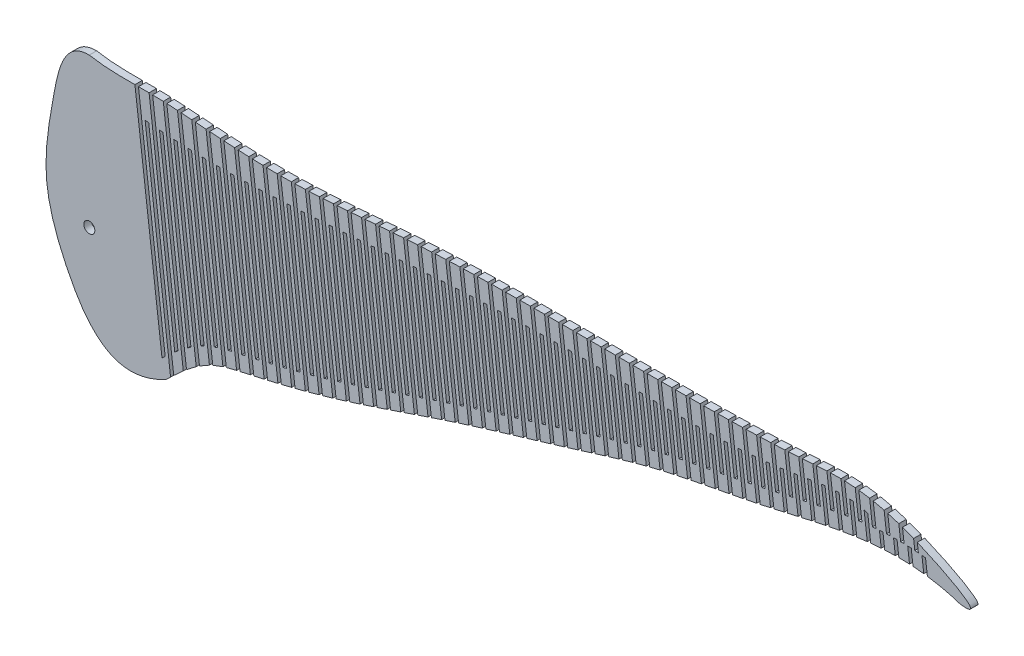
SolidWorks part; units mm, degrees
ref_plane "Front Plane" through (0, 0, 0) normal (0, 0, 1) x (1, 0, 0)
ref_plane "Top Plane" through (0, 0, 0) normal (0, 1, 0) x (1, 0, 0)
ref_plane "Right Plane" through (0, 0, 0) normal (1, 0, 0) x (0, 0, -1)
sketch "Sketch1" plane through (0, 0, 0) normal (0, 0, 1) x (1, 0, 0)
  line L0 (302.5, 350) -> (1512.5, 350) construction
  circle A0 centre (567.1336, 244.6808) radius 2.3812
  spline S0 degree 3 poles (600.4259, 204.6487) (606.7816, 210.8773) (616.6645, 220.058) (640.457, 225.1521) (675.3526, 233.403) (721.2401, 250.3771) (769.3486, 264.0871) (812.9063, 278.2152) (869.1744, 286.9675) (914.4097, 301.2518) (942.415, 291.7005) knots 0.067185 0.067185 0.067185 0.067185 0.134805 0.169915 0.254869 0.416958 0.551289 0.647146 0.774192 1 1 1 1
  spline S1 degree 3 poles (567.1336, 308.9768) (568.72, 308.6788) (577.9261, 307.3771) (593.7513, 308.2492) (620.2471, 306.2074) (657.6694, 303.8802) (709.4341, 310.0538) (762.3439, 310.4228) (816.8394, 310.2811) (875.3509, 310.7032) (908.5345, 316.1056) (953.925, 290.4379) (942.415, 291.7005) knots 0.040646 0.040646 0.040646 0.040646 0.052792 0.110595 0.156897 0.250722 0.388424 0.543858 0.641456 0.800742 0.941142 1 1 1 1
  spline S2 degree 3 poles (571.9268, 308.2818) (556.6626, 312.2623) (551.2163, 284.1495) (546.0116, 252.996) (559.7153, 216.0207) (577.7709, 191.9486) (600.4259, 204.6487) knots 0 0 0 0 0.228542 0.463661 0.652574 1 1 1 1
  dimension "D44" = 4.7625
  dimension "D1" = 548.9986
  dimension "D2" = 551.7183
  dimension "D3" = 557.9576
  dimension "D4" = 559.9938
  dimension "D5" = 567.1336
  dimension "D6" = 571.9268
  dimension "D7" = 595.2442
  dimension "D8" = 600.4259
  dimension "D9" = 613.8982
  dimension "D10" = 621.1525
  dimension "D11" = 634.1066
  dimension "D12" = 651.7242
  dimension "D13" = 665.7147
  dimension "D14" = 707.1679
  dimension "D15" = 724.7856
  dimension "D16" = 769.866
  dimension "D17" = 774.0113
  dimension "D18" = 809.2465
  dimension "D19" = 856.9177
  dimension "D20" = 873.499
  dimension "D21" = 925.8337
  dimension "D22" = 929.4609
  dimension "D23" = 942.415
  dimension "D24" = 946.0422
  dimension "D25" = 204.6487
  dimension "D26" = 220.1937
  dimension "D27" = 223.8208
  dimension "D28" = 231.5933
  dimension "D29" = 250.7654
  dimension "D30" = 265.7922
  dimension "D31" = 276.1555
  dimension "D32" = 286.0007
  dimension "D33" = 291.7005
  dimension "D34" = 295.3277
  dimension "D35" = 303.1001
  dimension "D36" = 305.1728
  dimension "D37" = 306.7273
  dimension "D38" = 307.7636
  dimension "D39" = 308.2818
  dimension "D40" = 308.8
  dimension "D41" = 308.9768
  dimension "D42" = 310.3545
  dimension "D43" = 311.9089
extrude "Boss-Extrude2" add sketch "Sketch1" along normal blind 3.175 contours S1 S2 S0 A0 | S1 S0 S2 region at (685.9886, 273.0456, 0)
sketch "Sketch3" plane through (0, 0, 3.175) normal (0, 0, 1) x (1, 0, 0)
  line L1 (586.2707, 312.0618) -> (598.4557, 211.5854)
  line L2 (587.7923, 312.0816) -> (599.8225, 212.8815)
  line L3 (591.1842, 296.6788) -> (603.0411, 198.9077)
  line L4 (592.7259, 296.5333) -> (604.5144, 199.3261)
  line L5 (592.3571, 312.1409) -> (603.9455, 216.5844)
  line L6 (593.8787, 312.1607) -> (605.3292, 217.741)
  line L7 (597.3447, 296.1474) -> (608.9342, 200.5812)
  line L8 (598.8823, 296.035) -> (610.4075, 200.9996)
  line L9 (598.4435, 312.22) -> (609.5153, 220.923)
  line L10 (599.9651, 312.2398) -> (610.9235, 221.8782)
  line L11 (603.4895, 295.7448) -> (614.8273, 202.2547)
  line L12 (605.0234, 295.6632) -> (616.3005, 202.6731)
  line L13 (604.5299, 312.2991) -> (615.1897, 224.3995)
  line L14 (606.0515, 312.3189) -> (616.6262, 225.1212)
  line L15 (609.6198, 295.4618) -> (620.7203, 203.9282)
  line L16 (611.1503, 295.4087) -> (622.1936, 204.3465)
  line L17 (610.6163, 312.3782) -> (620.9792, 226.9267)
  line L18 (612.1379, 312.398) -> (622.4433, 227.4209)
  line L19 (615.7368, 295.289) -> (626.6134, 205.6017)
  line L20 (617.264, 295.262) -> (628.0866, 206.02)
  line L21 (616.7027, 312.4574) -> (626.8637, 228.6709)
  line L22 (618.2243, 312.4771) -> (628.3439, 229.0317)
  line L23 (621.8415, 295.2173) -> (632.5064, 207.2751)
  line L24 (623.3659, 295.214) -> (633.9797, 207.6935)
  line L25 (622.7891, 312.5365) -> (632.7944, 230.034)
  line L26 (624.3107, 312.5563) -> (634.2786, 230.3625)
  line L27 (627.935, 295.2374) -> (638.3995, 208.9486)
  line L28 (629.4568, 295.2557) -> (639.8727, 209.367)
  line L29 (628.8755, 312.6156) -> (638.7293, 231.3625)
  line L30 (630.3971, 312.6354) -> (640.2122, 231.7014)
  line L31 (634.0185, 295.3404) -> (644.2925, 210.6221)
  line L32 (635.538, 295.3781) -> (645.7658, 211.0405)
  line L33 (634.9619, 312.6947) -> (644.6586, 232.737)
  line L34 (636.4835, 312.7145) -> (646.1399, 233.0892)
  line L35 (640.093, 295.5175) -> (650.1856, 212.2956)
  line L36 (641.6104, 295.5723) -> (651.6588, 212.7139)
  line L37 (641.0483, 312.7738) -> (650.5808, 234.1697)
  line L38 (642.5699, 312.7936) -> (652.0601, 234.5384)
  line L39 (646.1597, 295.7599) -> (656.0786, 213.9691)
  line L40 (647.6752, 295.8296) -> (657.5519, 214.3874)
  line L41 (647.1347, 312.853) -> (656.4945, 235.6732)
  line L42 (648.6563, 312.8727) -> (657.9714, 236.0616)
  line L43 (652.2194, 296.0586) -> (661.9717, 215.6425)
  line L44 (653.7334, 296.1411) -> (663.4449, 216.0609)
  line L45 (653.2211, 312.9321) -> (662.3981, 237.2602)
  line L46 (654.7427, 312.9518) -> (663.8722, 237.6715)
  line L47 (658.2734, 296.4052) -> (667.8647, 217.316)
  line L48 (659.7861, 296.4983) -> (669.338, 217.7344)
  line L49 (659.3076, 313.0112) -> (668.2902, 238.9415)
  line L50 (660.8292, 313.031) -> (669.7614, 239.3763)
  line L51 (664.3226, 296.791) -> (673.7578, 218.9895)
  line L52 (665.8343, 296.8926) -> (675.231, 219.4079)
  line L53 (665.394, 313.0903) -> (674.1715, 240.7113)
  line L54 (666.9156, 313.1101) -> (675.6404, 241.1658)
  line L55 (670.3681, 297.2075) -> (679.6508, 220.663)
  line L56 (671.879, 297.3153) -> (681.1241, 221.0813)
  line L57 (671.4804, 313.1694) -> (680.044, 242.5545)
  line L58 (673.002, 313.1892) -> (681.511, 243.0249)
  line L59 (676.4109, 297.646) -> (685.5439, 222.3365)
  line L60 (677.9213, 297.7581) -> (687.0172, 222.7548)
  line L61 (677.5668, 313.2485) -> (685.9094, 244.4559)
  line L62 (679.0884, 313.2683) -> (687.3749, 244.9385)
  line L63 (682.4521, 298.0982) -> (691.4369, 224.0099)
  line L64 (683.9622, 298.2124) -> (692.9102, 224.4283)
  line L65 (683.6532, 313.3277) -> (691.7696, 246.4003)
  line L66 (685.1748, 313.3474) -> (693.2341, 246.8913)
  line L67 (688.4926, 298.5557) -> (697.33, 225.6834)
  line L68 (690.0028, 298.6698) -> (698.8033, 226.1018)
  line L69 (689.7396, 313.4068) -> (697.6265, 248.3722)
  line L70 (691.2612, 313.4266) -> (699.0904, 248.8676)
  line L71 (694.5335, 299.0099) -> (703.2231, 227.3569)
  line L72 (696.0439, 299.122) -> (704.6963, 227.7753)
  line L73 (695.826, 313.4859) -> (703.4819, 250.3563)
  line L74 (697.3476, 313.5057) -> (704.9457, 250.8524)
  line L75 (700.5758, 299.4526) -> (709.1161, 229.0304)
  line L76 (702.0868, 299.5605) -> (710.5894, 229.4487)
  line L77 (701.9124, 313.565) -> (709.3376, 252.3374)
  line L78 (703.434, 313.5848) -> (710.8018, 252.8305)
  line L79 (706.6206, 299.8753) -> (715.0092, 230.7039)
  line L80 (708.1323, 299.9769) -> (716.4824, 231.1222)
  line L81 (707.9988, 313.6441) -> (715.1955, 254.3008)
  line L82 (709.5204, 313.6639) -> (716.6605, 254.7871)
  line L83 (712.6687, 300.2697) -> (720.9022, 232.3773)
  line L84 (714.1814, 300.363) -> (722.3755, 232.7957)
  line L85 (714.0852, 313.7232) -> (721.0573, 256.2318)
  line L86 (715.6068, 313.743) -> (722.5236, 256.7077)
  line L87 (718.7211, 300.63) -> (726.7953, 234.0508)
  line L88 (720.2348, 300.7146) -> (728.2685, 234.4692)
  line L89 (720.1716, 313.8024) -> (726.9247, 258.1173)
  line L90 (721.6932, 313.8221) -> (728.3924, 258.5814)
  line L91 (724.7776, 300.9552) -> (732.6883, 235.7243)
  line L92 (726.2924, 301.0309) -> (734.1616, 236.1427)
  line L93 (726.258, 313.8815) -> (732.7974, 259.9584)
  line L94 (727.7796, 313.9013) -> (734.2663, 260.4129)
  line L95 (730.8385, 301.2449) -> (738.5814, 237.3978)
  line L96 (732.3544, 301.3117) -> (740.0546, 237.8161)
  line L97 (732.3444, 313.9606) -> (738.6743, 261.7648)
  line L98 (733.866, 313.9804) -> (740.1441, 262.2121)
  line L99 (736.9037, 301.4986) -> (744.4744, 239.0713)
  line L100 (738.4207, 301.5564) -> (745.9477, 239.4896)
  line L101 (738.4308, 314.0397) -> (744.5543, 263.5461)
  line L102 (739.9524, 314.0595) -> (746.0246, 263.9886)
  line L103 (742.9734, 301.7159) -> (750.3675, 240.7447)
  line L104 (744.4915, 301.7645) -> (751.8407, 241.1631)
  line L105 (744.5172, 314.1188) -> (750.4361, 265.3121)
  line L106 (746.0388, 314.1386) -> (751.9067, 265.7524)
  line L107 (749.0475, 301.8963) -> (756.2605, 242.4182)
  line L108 (750.5667, 301.9355) -> (757.7338, 242.8366)
  line L109 (750.6036, 314.1979) -> (756.3186, 267.0727)
  line L110 (752.1252, 314.2177) -> (757.7892, 267.5132)
  line L111 (755.1262, 302.0391) -> (762.1536, 244.0917)
  line L112 (756.6465, 302.0689) -> (763.6268, 244.5101)
  line L113 (756.69, 314.2771) -> (762.2006, 268.8379)
  line L114 (758.2116, 314.2968) -> (763.6708, 269.2811)
  line L115 (761.2095, 302.1439) -> (768.0466, 245.7652)
  line L116 (762.731, 302.164) -> (769.5199, 246.1835)
  line L117 (762.7764, 314.3562) -> (768.0807, 270.6176)
  line L118 (764.298, 314.376) -> (769.5504, 271.0659)
  line L119 (767.2975, 302.2099) -> (773.9397, 247.4387)
  line L120 (768.8202, 302.2203) -> (775.413, 247.857)
  line L121 (768.8628, 314.4353) -> (773.958, 272.4215)
  line L122 (770.3844, 314.4551) -> (775.4268, 272.8764)
  line L123 (773.3902, 302.2365) -> (779.8327, 249.1121)
  line L124 (774.9142, 302.2369) -> (781.306, 249.5305)
  line L125 (774.9493, 314.5144) -> (779.8328, 274.2454)
  line L126 (776.4709, 314.5342) -> (781.3015, 274.7015)
  line L127 (779.4879, 302.2229) -> (785.7258, 250.7856)
  line L128 (781.0131, 302.2132) -> (787.1991, 251.204)
  line L129 (781.0357, 314.5935) -> (785.7084, 276.0628)
  line L130 (782.5573, 314.6133) -> (787.1778, 276.5128)
  line L131 (785.5905, 302.1685) -> (791.6188, 252.4591)
  line L132 (787.1169, 302.1484) -> (793.0921, 252.8775)
  line L133 (787.1221, 314.6727) -> (791.5882, 277.8453)
  line L134 (788.6437, 314.6924) -> (793.0592, 278.2822)
  line L135 (791.6981, 302.0727) -> (797.5119, 254.1326)
  line L136 (793.2257, 302.0431) -> (798.9852, 254.5509)
  line L137 (793.2085, 314.7518) -> (797.4757, 279.5649)
  line L138 (794.7301, 314.7715) -> (798.9491, 279.9818)
  line L139 (797.8096, 301.9448) -> (803.405, 255.8061)
  line L140 (799.3378, 301.9099) -> (804.8782, 256.2244)
  line L141 (799.2949, 314.8309) -> (803.3741, 281.1944)
  line L142 (800.8165, 314.8507) -> (804.8507, 281.5844)
  line L143 (803.9227, 301.8034) -> (809.298, 257.4795)
  line L144 (805.451, 301.7683) -> (810.7713, 257.8979)
  line L145 (805.3813, 314.91) -> (809.2866, 282.707)
  line L146 (806.9029, 314.9298) -> (810.7672, 283.0648)
  line L147 (810.0352, 301.6681) -> (815.1911, 259.153)
  line L148 (811.5629, 301.6375) -> (816.6643, 259.5714)
  line L149 (811.4677, 314.9891) -> (815.2144, 284.0942)
  line L150 (812.9893, 315.0089) -> (816.6984, 284.424)
  line L151 (816.1445, 301.5583) -> (821.0841, 260.8265)
  line L152 (817.671, 301.5371) -> (822.5574, 261.2449)
  line L153 (817.5541, 315.0682) -> (821.1545, 285.3794)
  line L154 (819.0757, 315.088) -> (822.6411, 285.6879)
  line L155 (822.2484, 301.4932) -> (826.9772, 262.5)
  line L156 (823.7732, 301.4861) -> (828.4504, 262.9183)
  line L157 (823.6405, 315.1474) -> (827.1037, 286.5897)
  line L158 (825.1621, 315.1671) -> (828.5921, 286.8839)
  line L159 (828.3446, 301.4916) -> (832.8702, 264.1735)
  line L160 (829.8671, 301.5033) -> (834.3435, 264.5918)
  line L161 (829.7269, 315.2265) -> (833.0587, 287.753)
  line L162 (831.2485, 315.2463) -> (834.5479, 288.0398)
  line L163 (834.4309, 301.5716) -> (838.7633, 265.8469)
  line L164 (835.9506, 301.6065) -> (840.2365, 266.2653)
  line L165 (835.8133, 315.3056) -> (839.0159, 288.897)
  line L166 (837.3349, 315.3254) -> (840.5052, 289.1831)
  line L167 (840.5051, 301.7507) -> (844.6563, 267.5204)
  line L168 (842.0216, 301.8129) -> (846.1296, 267.9388)
  line L169 (841.8997, 315.3847) -> (844.9723, 290.0488)
  line L170 (843.4213, 315.4045) -> (846.4608, 290.3412)
  line L171 (846.5654, 302.0454) -> (850.5494, 269.1939)
  line L172 (848.0781, 302.1389) -> (852.0226, 269.6123)
  line L173 (847.9861, 315.4638) -> (850.9243, 291.2359)
  line L174 (849.5077, 315.4836) -> (852.4112, 291.5415)
  line L175 (852.6098, 302.4709) -> (856.4424, 270.8674)
  line L176 (854.1182, 302.5994) -> (857.9157, 271.2857)
  line L177 (854.0725, 315.5429) -> (856.8687, 292.4861)
  line L178 (855.5941, 315.5627) -> (858.3533, 292.8104)
  line L179 (858.6366, 303.0415) -> (862.3355, 272.5409)
  line L180 (860.1404, 303.2083) -> (863.8087, 272.9592)
  line L181 (860.1589, 315.6221) -> (862.8047, 293.8049)
  line L182 (861.6805, 315.6418) -> (864.288, 294.1412)
  line L183 (864.6442, 303.7702) -> (868.2285, 274.2143)
  line L184 (866.143, 303.9784) -> (869.7018, 274.6327)
  line L185 (866.2453, 315.7012) -> (868.737, 295.1554)
  line L186 (867.7669, 315.721) -> (870.22, 295.4931)
  line L187 (870.6314, 304.668) -> (874.1216, 275.8878)
  line L188 (872.1252, 304.9163) -> (875.5949, 276.3062)
  line L189 (872.3317, 315.7803) -> (874.6704, 296.4959)
  line L190 (873.8533, 315.8001) -> (876.1545, 296.8247)
  line L191 (876.6053, 305.6744) -> (880.0146, 277.5613)
  line L192 (878.0994, 305.9207) -> (881.4879, 277.9797)
  line L193 (878.4181, 315.8594) -> (880.6099, 297.7861)
  line L194 (879.9397, 315.8792) -> (882.0963, 298.096)
  line L195 (882.59, 306.5925) -> (885.9077, 279.2348)
  line L196 (884.091, 306.7821) -> (887.381, 279.6531)
  line L197 (884.5045, 315.9385) -> (886.5605, 298.9855)
  line L198 (886.0261, 315.9583) -> (888.0504, 299.2664)
  line L199 (888.6132, 307.1928) -> (891.8008, 280.9083)
  line L200 (890.1288, 307.2619) -> (893.274, 281.3266)
  line L201 (890.591, 316.0176) -> (892.527, 300.0536)
  line L202 (892.1126, 316.0374) -> (894.0216, 300.2954)
  line L203 (894.7094, 307.191) -> (897.6938, 282.5817)
  line L204 (896.2501, 307.0528) -> (899.1671, 283.0001)
  line L205 (896.6774, 316.0968) -> (898.5142, 300.9503)
  line L206 (898.199, 316.1165) -> (900.0148, 301.1429)
  line L207 (900.9283, 306.1771) -> (903.5869, 284.2552)
  line L208 (902.5109, 305.6944) -> (905.0601, 284.6736)
  line L209 (902.7638, 316.1759) -> (904.5273, 301.6343)
  line L210 (904.2854, 316.1957) -> (906.0352, 301.767)
  line L211 (907.5451, 301.883) -> (909.4799, 285.9287)
  line L212 (909.0571, 301.9817) -> (910.9532, 286.3471)
  line L213 (908.8502, 316.255) -> (910.5714, 302.0623)
  line L214 (910.3718, 316.2748) -> (912.0879, 302.1241)
  line L215 (913.6067, 302.1664) -> (915.373, 287.6022)
  line L216 (915.1281, 302.1883) -> (916.8462, 288.0205)
  line L217 (914.9366, 316.3341) -> (916.6519, 302.1893)
  line L218 (916.4582, 316.3539) -> (918.1785, 302.1685)
  line L219 (919.7077, 302.1251) -> (921.266, 289.2757)
  line L220 (921.2398, 302.0584) -> (922.7393, 289.694)
  line L221 (921.023, 316.4132) -> (922.7749, 301.9674)
  line L222 (922.5446, 316.433) -> (924.3129, 301.8515)
  line L223 (925.8541, 301.7098) -> (927.1591, 290.9491)
  line L224 (927.3985, 301.5413) -> (928.6323, 291.3675)
  line L225 (586.2707, 312.0618) -> (587.7923, 312.0816)
  line L226 (603.0411, 198.9077) -> (604.5144, 199.3261)
  line L229 (592.3571, 312.1409) -> (593.8787, 312.1607)
  line L230 (598.4435, 312.22) -> (599.9651, 312.2398)
  line L231 (604.5299, 312.2991) -> (606.0515, 312.3189)
  line L232 (610.6163, 312.3782) -> (612.1379, 312.398)
  line L233 (616.7027, 312.4574) -> (618.2243, 312.4771)
  line L234 (622.7891, 312.5365) -> (624.3107, 312.5563)
  line L235 (628.8755, 312.6156) -> (630.3971, 312.6354)
  line L236 (634.9619, 312.6947) -> (636.4835, 312.7145)
  line L237 (641.0483, 312.7738) -> (642.5699, 312.7936)
  line L238 (647.1347, 312.853) -> (648.6563, 312.8727)
  line L239 (653.2211, 312.9321) -> (654.7427, 312.9518)
  line L240 (659.3076, 313.0112) -> (660.8292, 313.031)
  line L241 (665.394, 313.0903) -> (666.9156, 313.1101)
  line L242 (671.4804, 313.1694) -> (673.002, 313.1892)
  line L243 (677.5668, 313.2485) -> (679.0884, 313.2683)
  line L244 (683.6532, 313.3277) -> (685.1748, 313.3474)
  line L245 (689.7396, 313.4068) -> (691.2612, 313.4266)
  line L246 (701.9124, 313.565) -> (703.434, 313.5848)
  line L247 (707.9988, 313.6441) -> (709.5204, 313.6639)
  line L248 (695.826, 313.4859) -> (697.3476, 313.5057)
  line L249 (714.0852, 313.7232) -> (715.6068, 313.743)
  line L250 (720.1716, 313.8024) -> (721.6932, 313.8221)
  line L251 (726.258, 313.8815) -> (727.7796, 313.9013)
  line L252 (732.3444, 313.9606) -> (733.866, 313.9804)
  line L253 (738.4308, 314.0397) -> (739.9524, 314.0595)
  line L254 (744.5172, 314.1188) -> (746.0388, 314.1386)
  line L255 (750.6036, 314.1979) -> (752.1252, 314.2177)
  line L256 (756.69, 314.2771) -> (758.2116, 314.2968)
  line L257 (762.7764, 314.3562) -> (764.298, 314.376)
  line L258 (768.8628, 314.4353) -> (770.3844, 314.4551)
  line L259 (774.9493, 314.5144) -> (776.4709, 314.5342)
  line L260 (781.0357, 314.5935) -> (782.5573, 314.6133)
  line L261 (787.1221, 314.6727) -> (788.6437, 314.6924)
  line L262 (793.2085, 314.7518) -> (794.7301, 314.7715)
  line L263 (799.2949, 314.8309) -> (800.8165, 314.8507)
  line L264 (805.3813, 314.91) -> (806.9029, 314.9298)
  line L265 (811.4677, 314.9891) -> (812.9893, 315.0089)
  line L266 (823.6405, 315.1474) -> (825.1621, 315.1671)
  line L267 (817.5541, 315.0682) -> (819.0757, 315.088)
  line L268 (829.7269, 315.2265) -> (831.2485, 315.2463)
  line L269 (841.8997, 315.3847) -> (843.4213, 315.4045)
  line L270 (835.8133, 315.3056) -> (837.3349, 315.3254)
  line L271 (847.9861, 315.4638) -> (849.5077, 315.4836)
  line L272 (854.0725, 315.5429) -> (855.5941, 315.5627)
  line L273 (860.1589, 315.6221) -> (861.6805, 315.6418)
  line L274 (866.2453, 315.7012) -> (867.7669, 315.721)
  line L275 (872.3317, 315.7803) -> (873.8533, 315.8001)
  line L276 (878.4181, 315.8594) -> (879.9397, 315.8792)
  line L277 (884.5045, 315.9385) -> (886.0261, 315.9583)
  line L278 (890.591, 316.0176) -> (892.1126, 316.0374)
  line L279 (902.7638, 316.1759) -> (904.2854, 316.1957)
  line L280 (896.6774, 316.0968) -> (898.199, 316.1165)
  line L281 (908.8502, 316.255) -> (910.3718, 316.2748)
  line L282 (914.9366, 316.3341) -> (916.4582, 316.3539)
  line L283 (921.023, 316.4132) -> (922.5446, 316.433)
  line L284 (927.1591, 290.9491) -> (928.6323, 291.3675)
  line L285 (921.266, 289.2757) -> (922.7393, 289.694)
  line L286 (915.373, 287.6022) -> (916.8462, 288.0205)
  line L287 (909.4799, 285.9287) -> (910.9532, 286.3471)
  line L288 (903.5869, 284.2552) -> (905.0601, 284.6736)
  line L289 (897.6938, 282.5817) -> (899.1671, 283.0001)
  line L290 (891.8008, 280.9083) -> (893.274, 281.3266)
  line L291 (832.8702, 264.1735) -> (834.3435, 264.5918)
  line L292 (838.7633, 265.8469) -> (840.2365, 266.2653)
  line L293 (844.6563, 267.5204) -> (846.1296, 267.9388)
  line L294 (850.5494, 269.1939) -> (852.0226, 269.6123)
  line L295 (856.4424, 270.8674) -> (857.9157, 271.2857)
  line L296 (862.3355, 272.5409) -> (863.8087, 272.9592)
  line L297 (868.2285, 274.2143) -> (869.7018, 274.6327)
  line L298 (874.1216, 275.8878) -> (875.5949, 276.3062)
  line L299 (880.0146, 277.5613) -> (881.4879, 277.9797)
  line L300 (885.9077, 279.2348) -> (887.381, 279.6531)
  line L301 (750.3675, 240.7447) -> (751.8407, 241.1631)
  line L302 (756.2605, 242.4182) -> (757.7338, 242.8366)
  line L303 (762.1536, 244.0917) -> (763.6268, 244.5101)
  line L304 (768.0466, 245.7652) -> (769.5199, 246.1835)
  line L305 (773.9397, 247.4387) -> (775.413, 247.857)
  line L306 (779.8327, 249.1121) -> (781.306, 249.5305)
  line L307 (785.7258, 250.7856) -> (787.1991, 251.204)
  line L308 (791.6188, 252.4591) -> (793.0921, 252.8775)
  line L309 (797.5119, 254.1326) -> (798.9852, 254.5509)
  line L310 (803.405, 255.8061) -> (804.8782, 256.2244)
  line L311 (809.298, 257.4795) -> (810.7713, 257.8979)
  line L312 (815.1911, 259.153) -> (816.6643, 259.5714)
  line L313 (821.0841, 260.8265) -> (822.5574, 261.2449)
  line L314 (826.9772, 262.5) -> (828.4504, 262.9183)
  line L315 (661.9717, 215.6425) -> (663.4449, 216.0609)
  line L316 (667.8647, 217.316) -> (669.338, 217.7344)
  line L317 (673.7578, 218.9895) -> (675.231, 219.4079)
  line L318 (679.6508, 220.663) -> (681.1241, 221.0813)
  line L319 (685.5439, 222.3365) -> (687.0172, 222.7548)
  line L320 (691.4369, 224.0099) -> (692.9102, 224.4283)
  line L321 (697.33, 225.6834) -> (698.8033, 226.1018)
  line L322 (703.2231, 227.3569) -> (704.6963, 227.7753)
  line L323 (709.1161, 229.0304) -> (710.5894, 229.4487)
  line L324 (715.0092, 230.7039) -> (716.4824, 231.1222)
  line L325 (720.9022, 232.3773) -> (722.3755, 232.7957)
  line L326 (726.7953, 234.0508) -> (728.2685, 234.4692)
  line L327 (732.6883, 235.7243) -> (734.1616, 236.1427)
  line L328 (738.5814, 237.3978) -> (740.0546, 237.8161)
  line L329 (744.4744, 239.0713) -> (745.9477, 239.4896)
  line L330 (656.0786, 213.9691) -> (657.5519, 214.3874)
  line L331 (614.8273, 202.2547) -> (616.3005, 202.6731)
  line L332 (608.9342, 200.5812) -> (610.4075, 200.9996)
  line L333 (620.7203, 203.9282) -> (622.1936, 204.3465)
  line L334 (626.6134, 205.6017) -> (628.0866, 206.02)
  line L335 (638.3995, 208.9486) -> (639.8727, 209.367)
  line L336 (644.2925, 210.6221) -> (645.7658, 211.0405)
  line L337 (650.1856, 212.2956) -> (651.6588, 212.7139)
  line L338 (632.5064, 207.2751) -> (633.9797, 207.6935)
  spline S0 degree 3 poles (632.7944, 230.034) (633.1444, 230.1112) (633.4931, 230.1883) (633.9877, 230.298) (634.1332, 230.3302) (634.2786, 230.3625) knots 0.110286 0.110286 0.110286 0.110286 0.113281 0.113281 0.11453 0.11453 0.11453 0.11453
  spline S1 degree 3 poles (900.9283, 306.1771) (901.4603, 306.0325) (901.9879, 305.8719) (902.5109, 305.6944) knots 0.94529 0.94529 0.94529 0.94529 0.950484 0.950484 0.950484 0.950484
  spline S2 degree 3 poles (894.7094, 307.191) (895.2258, 307.1554) (895.7395, 307.1096) (896.2501, 307.0528) knots 0.925603 0.925603 0.925603 0.925603 0.930387 0.930387 0.930387 0.930387
  spline S3 degree 3 poles (891.6495, 307.2887) (892.1607, 307.2899) (892.6696, 307.283) (893.1761, 307.2672) knots 0.916249 0.916249 0.916249 0.916249 0.920894 0.920894 0.920894 0.920894
  spline S4 degree 3 poles (888.6132, 307.1928) (889.1202, 307.2225) (889.6255, 307.2457) (890.1288, 307.2619) knots 0.907128 0.907128 0.907128 0.907128 0.911663 0.911663 0.911663 0.911663
  spline S5 degree 3 poles (925.8541, 301.7098) (926.3687, 301.6581) (926.8835, 301.602) (927.3985, 301.5413) knots 0.95076 0.95076 0.95076 0.95076 0.954851 0.954851 0.954851 0.954851
  spline S6 degree 3 poles (922.7749, 301.9674) (923.2873, 301.933) (923.8, 301.8944) (924.3129, 301.8515) knots 0.942591 0.942591 0.942591 0.942591 0.946673 0.946673 0.946673 0.946673
  spline S7 degree 3 poles (598.4557, 211.5854) (598.9074, 212.0181) (599.3629, 212.4504) (599.8225, 212.8815) knots 0.009171 0.009171 0.009171 0.009171 0.014124 0.014124 0.014124 0.014124
  spline S8 degree 3 poles (919.7077, 302.1251) (920.0912, 302.1113) (920.4748, 302.0954) (920.9856, 302.0712) (921.1127, 302.0649) (921.2398, 302.0584) knots 0.934439 0.934439 0.934439 0.934439 0.9375 0.9375 0.938514 0.938514 0.938514 0.938514
  spline S9 degree 3 poles (916.6519, 302.1893) (917.1605, 302.186) (917.6693, 302.1791) (918.1785, 302.1685) knots 0.926298 0.926298 0.926298 0.926298 0.930367 0.930367 0.930367 0.930367
  spline S10 degree 3 poles (913.6067, 302.1664) (914.1135, 302.1771) (914.6206, 302.1845) (915.1281, 302.1883) knots 0.918165 0.918165 0.918165 0.918165 0.922231 0.922231 0.922231 0.922231
  spline S11 degree 3 poles (910.5714, 302.0623) (911.0765, 302.0861) (911.582, 302.1067) (912.0879, 302.1241) knots 0.910037 0.910037 0.910037 0.910037 0.914101 0.914101 0.914101 0.914101
  spline S12 degree 3 poles (907.5451, 301.883) (908.0487, 301.9189) (908.5527, 301.9518) (909.0571, 301.9817) knots 0.901909 0.901909 0.901909 0.901909 0.905973 0.905973 0.905973 0.905973
  spline S13 degree 3 poles (904.5273, 301.6343) (905.0295, 301.6812) (905.5321, 301.7255) (906.0352, 301.767) knots 0.893779 0.893779 0.893779 0.893779 0.897844 0.897844 0.897844 0.897844
  spline S14 degree 3 poles (898.5142, 300.9503) (899.014, 301.0167) (899.5142, 301.081) (900.0148, 301.1429) knots 0.877505 0.877505 0.877505 0.877505 0.881576 0.881576 0.881576 0.881576
  spline S15 degree 3 poles (886.5605, 298.9855) (887.0567, 299.0805) (887.5533, 299.1741) (888.0504, 299.2664) knots 0.844835 0.844835 0.844835 0.844835 0.848931 0.848931 0.848931 0.848931
  spline S16 degree 3 poles (892.527, 300.0536) (893.0248, 300.136) (893.523, 300.2166) (894.0216, 300.2954) knots 0.861196 0.861196 0.861196 0.861196 0.865278 0.865278 0.865278 0.865278
  spline S17 degree 3 poles (882.59, 306.5925) (883.0914, 306.6594) (883.5918, 306.7228) (884.091, 306.7821) knots 0.889384 0.889384 0.889384 0.889384 0.893771 0.893771 0.893771 0.893771
  spline S18 degree 3 poles (876.6053, 305.6744) (877.1038, 305.7577) (877.6019, 305.84) (878.0994, 305.9207) knots 0.872038 0.872038 0.872038 0.872038 0.876353 0.876353 0.876353 0.876353
  spline S19 degree 3 poles (880.6099, 297.7861) (881.105, 297.8903) (881.6004, 297.9937) (882.0963, 298.096) knots 0.828405 0.828405 0.828405 0.828405 0.83252 0.83252 0.83252 0.83252
  spline S20 degree 3 poles (870.6314, 304.668) (871.1291, 304.7496) (871.6271, 304.8325) (872.1252, 304.9163) knots 0.854825 0.854825 0.854825 0.854825 0.859129 0.859129 0.859129 0.859129
  spline S21 degree 3 poles (874.6704, 296.4959) (874.7436, 296.5122) (874.8167, 296.5285) (875.3111, 296.6384) (875.7327, 296.7317) (876.1545, 296.8247) knots 0.811887 0.811887 0.811887 0.811887 0.8125 0.8125 0.816026 0.816026 0.816026 0.816026
  spline S22 degree 3 poles (864.6442, 303.7702) (865.1434, 303.8377) (865.643, 303.9071) (866.143, 303.9784) knots 0.837517 0.837517 0.837517 0.837517 0.84186 0.84186 0.84186 0.84186
  spline S23 degree 3 poles (868.737, 295.1554) (869.2308, 295.268) (869.7252, 295.3806) (870.22, 295.4931) knots 0.795263 0.795263 0.795263 0.795263 0.79943 0.79943 0.79943 0.79943
  spline S24 degree 3 poles (867.6404, 304.1975) (868.1387, 304.2722) (868.6374, 304.3489) (869.1365, 304.4275) knots 0.846192 0.846192 0.846192 0.846192 0.850514 0.850514 0.850514 0.850514
  spline S25 degree 3 poles (858.6366, 303.0415) (859.1375, 303.0954) (859.6388, 303.151) (860.1404, 303.2083) knots 0.820044 0.820044 0.820044 0.820044 0.824427 0.824427 0.824427 0.824427
  spline S26 degree 3 poles (862.8047, 293.8049) (863.1271, 293.8778) (863.4496, 293.9509) (863.9442, 294.0631) (864.116, 294.1022) (864.288, 294.1412) knots 0.778507 0.778507 0.778507 0.778507 0.78125 0.78125 0.78271 0.78271 0.78271 0.78271
  spline S27 degree 3 poles (855.6255, 302.7372) (856.1272, 302.7846) (856.6293, 302.8337) (857.1316, 302.8845) knots 0.811249 0.811249 0.811249 0.811249 0.815651 0.815651 0.815651 0.815651
  spline S28 degree 3 poles (856.8687, 292.4861) (857.338, 292.5879) (857.8077, 292.6904) (858.3031, 292.7994) (858.3282, 292.8049) (858.3533, 292.8104) knots 0.761595 0.761595 0.761595 0.761595 0.765625 0.765625 0.76584 0.76584 0.76584 0.76584
  spline S29 degree 3 poles (850.9243, 291.2359) (851.4201, 291.3371) (851.9157, 291.439) (852.4112, 291.5415) knots 0.744565 0.744565 0.744565 0.744565 0.748822 0.748822 0.748822 0.748822
  spline S30 degree 3 poles (844.9723, 290.0488) (845.4686, 290.1458) (845.9648, 290.2433) (846.4608, 290.3412) knots 0.727549 0.727549 0.727549 0.727549 0.7318 0.7318 0.7318 0.7318
  spline S31 degree 3 poles (839.0159, 288.897) (839.5125, 288.9923) (840.0089, 289.0876) (840.5052, 289.1831) knots 0.710559 0.710559 0.710559 0.710559 0.714803 0.714803 0.714803 0.714803
  spline S32 degree 3 poles (833.0587, 287.753) (833.5552, 287.8488) (834.0516, 287.9444) (834.5479, 288.0398) knots 0.693602 0.693602 0.693602 0.693602 0.697838 0.697838 0.697838 0.697838
  spline S33 degree 3 poles (852.6098, 302.4709) (853.1123, 302.5121) (853.6151, 302.555) (854.1182, 302.5994) knots 0.802417 0.802417 0.802417 0.802417 0.806837 0.806837 0.806837 0.806837
  spline S34 degree 3 poles (846.5654, 302.0454) (847.0693, 302.0751) (847.5736, 302.1063) (848.0781, 302.1389) knots 0.78465 0.78465 0.78465 0.78465 0.789104 0.789104 0.789104 0.789104
  spline S35 degree 3 poles (840.5051, 301.7507) (841.0104, 301.7702) (841.5159, 301.791) (842.0216, 301.8129) knots 0.766757 0.766757 0.766757 0.766757 0.771241 0.771241 0.771241 0.771241
  spline S36 degree 3 poles (834.4309, 301.5716) (834.9372, 301.5822) (835.4438, 301.5938) (835.9506, 301.6065) knots 0.748755 0.748755 0.748755 0.748755 0.753265 0.753265 0.753265 0.753265
  spline S37 degree 3 poles (828.3446, 301.4916) (828.8519, 301.4946) (829.3595, 301.4985) (829.8671, 301.5033) knots 0.730661 0.730661 0.730661 0.730661 0.735192 0.735192 0.735192 0.735192
  spline S38 degree 3 poles (827.1037, 286.5897) (827.6, 286.6883) (828.0961, 286.7863) (828.5921, 286.8839) knots 0.676684 0.676684 0.676684 0.676684 0.680909 0.680909 0.680909 0.680909
  spline S39 degree 3 poles (821.1545, 285.3794) (821.6501, 285.483) (822.1457, 285.5858) (822.6411, 285.6879) knots 0.65981 0.65981 0.65981 0.65981 0.664024 0.664024 0.664024 0.664024
  spline S40 degree 3 poles (822.2484, 301.4932) (822.7565, 301.4902) (823.2648, 301.4878) (823.7732, 301.4861) knots 0.712492 0.712492 0.712492 0.712492 0.71704 0.71704 0.71704 0.71704
  spline S41 degree 3 poles (816.1445, 301.5583) (816.6533, 301.5508) (817.1621, 301.5437) (817.671, 301.5371) knots 0.694267 0.694267 0.694267 0.694267 0.698828 0.698828 0.698828 0.698828
  spline S42 degree 3 poles (810.0352, 301.6681) (810.5444, 301.6577) (811.0536, 301.6474) (811.5629, 301.6375) knots 0.676006 0.676006 0.676006 0.676006 0.680573 0.680573 0.680573 0.680573
  spline S43 degree 3 poles (803.9227, 301.8034) (804.4322, 301.7916) (804.9416, 301.7799) (805.451, 301.7683) knots 0.657727 0.657727 0.657727 0.657727 0.662297 0.662297 0.662297 0.662297
  spline S44 degree 3 poles (809.2866, 282.707) (809.7802, 282.8276) (810.2737, 282.9469) (810.7672, 283.0648) knots 0.626211 0.626211 0.626211 0.626211 0.630399 0.630399 0.630399 0.630399
  spline S45 degree 3 poles (803.3741, 281.1944) (803.8657, 281.3255) (804.3579, 281.4556) (804.8507, 281.5844) knots 0.609452 0.609452 0.609452 0.609452 0.613649 0.613649 0.613649 0.613649
  spline S46 degree 3 poles (797.4757, 279.5649) (797.6091, 279.603) (797.7425, 279.6409) (798.2335, 279.7803) (798.5912, 279.8813) (798.9491, 279.9818) knots 0.592602 0.592602 0.592602 0.592602 0.59375 0.59375 0.596823 0.596823 0.596823 0.596823
  spline S47 degree 3 poles (791.5882, 277.8453) (792.0781, 277.9915) (792.5685, 278.1372) (793.0592, 278.2822) knots 0.575659 0.575659 0.575659 0.575659 0.579903 0.579903 0.579903 0.579903
  spline S48 degree 3 poles (815.2144, 284.0942) (815.7091, 284.2052) (816.2038, 284.3151) (816.6984, 284.424) knots 0.642984 0.642984 0.642984 0.642984 0.647186 0.647186 0.647186 0.647186
  spline S49 degree 3 poles (785.7084, 276.0628) (786.1528, 276.1993) (786.5975, 276.3355) (787.0876, 276.4853) (787.1327, 276.499) (787.1778, 276.5128) knots 0.558626 0.558626 0.558626 0.558626 0.5625 0.5625 0.562892 0.562892 0.562892 0.562892
  spline S50 degree 3 poles (773.958, 272.4215) (774.4473, 272.5728) (774.9369, 272.7245) (775.4268, 272.8764) knots 0.524301 0.524301 0.524301 0.524301 0.52861 0.52861 0.52861 0.52861
  spline S51 degree 3 poles (779.8328, 274.2454) (780.322, 274.3974) (780.8116, 274.5495) (781.3015, 274.7015) knots 0.541506 0.541506 0.541506 0.541506 0.545794 0.545794 0.545794 0.545794
  spline S52 degree 3 poles (791.6981, 302.0727) (792.2074, 302.0632) (792.7166, 302.0533) (793.2257, 302.0431) knots 0.621199 0.621199 0.621199 0.621199 0.625759 0.625759 0.625759 0.625759
  spline S53 degree 3 poles (797.8096, 301.9448) (798.3191, 301.9333) (798.8285, 301.9217) (799.3378, 301.9099) knots 0.639452 0.639452 0.639452 0.639452 0.644019 0.644019 0.644019 0.644019
  spline S54 degree 3 poles (785.5905, 302.1685) (786.0994, 302.1622) (786.6082, 302.1555) (787.1169, 302.1484) knots 0.602988 0.602988 0.602988 0.602988 0.607536 0.607536 0.607536 0.607536
  spline S55 degree 3 poles (779.4879, 302.2229) (779.9964, 302.2201) (780.5048, 302.2169) (781.0131, 302.2132) knots 0.584826 0.584826 0.584826 0.584826 0.589362 0.589362 0.589362 0.589362
  spline S56 degree 3 poles (773.3902, 302.2365) (773.8983, 302.237) (774.4063, 302.2372) (774.9142, 302.2369) knots 0.566709 0.566709 0.566709 0.566709 0.571235 0.571235 0.571235 0.571235
  spline S57 degree 3 poles (767.2975, 302.2099) (767.8051, 302.2137) (768.3127, 302.2172) (768.8202, 302.2203) knots 0.548633 0.548633 0.548633 0.548633 0.553149 0.553149 0.553149 0.553149
  spline S58 degree 3 poles (761.2095, 302.1439) (761.7167, 302.151) (762.2239, 302.1577) (762.731, 302.164) knots 0.530593 0.530593 0.530593 0.530593 0.5351 0.5351 0.5351 0.5351
  spline S59 degree 3 poles (755.1262, 302.0391) (755.633, 302.0494) (756.1398, 302.0594) (756.6465, 302.0689) knots 0.512584 0.512584 0.512584 0.512584 0.517084 0.517084 0.517084 0.517084
  spline S60 degree 3 poles (749.0475, 301.8963) (749.5539, 301.9097) (750.0603, 301.9228) (750.5667, 301.9355) knots 0.494603 0.494603 0.494603 0.494603 0.499096 0.499096 0.499096 0.499096
  spline S61 degree 3 poles (736.9037, 301.4986) (737.4094, 301.5182) (737.9151, 301.5375) (738.4207, 301.5564) knots 0.458706 0.458706 0.458706 0.458706 0.463189 0.463189 0.463189 0.463189
  spline S62 degree 3 poles (742.9734, 301.7159) (743.4794, 301.7325) (743.9855, 301.7487) (744.4915, 301.7645) knots 0.476645 0.476645 0.476645 0.476645 0.481133 0.481133 0.481133 0.481133
  spline S63 degree 3 poles (724.7776, 300.9552) (725.2825, 300.9808) (725.7875, 301.0061) (726.2924, 301.0309) knots 0.42287 0.42287 0.42287 0.42287 0.427347 0.427347 0.427347 0.427347
  spline S64 degree 3 poles (730.8385, 301.2449) (731.3438, 301.2675) (731.8491, 301.2898) (732.3544, 301.3117) knots 0.440782 0.440782 0.440782 0.440782 0.445262 0.445262 0.445262 0.445262
  spline S65 degree 3 poles (706.6206, 299.8753) (707.1244, 299.9095) (707.6283, 299.9433) (708.1323, 299.9769) knots 0.369156 0.369156 0.369156 0.369156 0.373632 0.373632 0.373632 0.373632
  spline S66 degree 3 poles (718.7211, 300.63) (719.2256, 300.6585) (719.7302, 300.6867) (720.2348, 300.7146) knots 0.404963 0.404963 0.404963 0.404963 0.40944 0.40944 0.40944 0.40944
  spline S67 degree 3 poles (700.5758, 299.4526) (701.0794, 299.4888) (701.5831, 299.5247) (702.0868, 299.5605) knots 0.351249 0.351249 0.351249 0.351249 0.355726 0.355726 0.355726 0.355726
  spline S68 degree 3 poles (712.6687, 300.2697) (713.1729, 300.3012) (713.6772, 300.3323) (714.1814, 300.363) knots 0.38706 0.38706 0.38706 0.38706 0.391536 0.391536 0.391536 0.391536
  spline S69 degree 3 poles (682.4521, 298.0982) (682.9554, 298.1362) (683.4588, 298.1743) (683.9622, 298.2124) knots 0.297493 0.297493 0.297493 0.297493 0.301975 0.301975 0.301975 0.301975
  spline S70 degree 3 poles (694.5335, 299.0099) (695.037, 299.0474) (695.5404, 299.0848) (696.0439, 299.122) knots 0.333337 0.333337 0.333337 0.333337 0.337815 0.337815 0.337815 0.337815
  spline S71 degree 3 poles (676.4109, 297.646) (676.9144, 297.6832) (677.4178, 297.7206) (677.9213, 297.7581) knots 0.279559 0.279559 0.279559 0.279559 0.284043 0.284043 0.284043 0.284043
  spline S72 degree 3 poles (688.4926, 298.5557) (688.996, 298.5938) (689.4993, 298.6318) (690.0028, 298.6698) knots 0.315419 0.315419 0.315419 0.315419 0.319899 0.319899 0.319899 0.319899
  spline S73 degree 3 poles (670.3681, 297.2075) (670.8717, 297.2432) (671.3754, 297.2792) (671.879, 297.3153) knots 0.261614 0.261614 0.261614 0.261614 0.266101 0.266101 0.266101 0.266101
  spline S74 degree 3 poles (664.3226, 296.791) (664.8265, 296.8246) (665.3304, 296.8584) (665.8343, 296.8926) knots 0.243658 0.243658 0.243658 0.243658 0.248148 0.248148 0.248148 0.248148
  spline S75 degree 3 poles (658.2734, 296.4052) (658.7776, 296.4359) (659.2819, 296.4669) (659.7861, 296.4983) knots 0.225689 0.225689 0.225689 0.225689 0.230182 0.230182 0.230182 0.230182
  spline S76 degree 3 poles (652.2194, 296.0586) (652.7241, 296.0856) (653.2288, 296.1132) (653.7334, 296.1411) knots 0.207705 0.207705 0.207705 0.207705 0.212202 0.212202 0.212202 0.212202
  spline S77 degree 3 poles (627.935, 295.2374) (628.4423, 295.2426) (628.9496, 295.2488) (629.4568, 295.2557) knots 0.135596 0.135596 0.135596 0.135596 0.140112 0.140112 0.140112 0.140112
  spline S78 degree 3 poles (646.1597, 295.7599) (646.6649, 295.7825) (647.17, 295.8058) (647.6752, 295.8296) knots 0.189705 0.189705 0.189705 0.189705 0.194207 0.194207 0.194207 0.194207
  spline S79 degree 3 poles (640.093, 295.5175) (640.5988, 295.5351) (641.1046, 295.5534) (641.6104, 295.5723) knots 0.171688 0.171688 0.171688 0.171688 0.176194 0.176194 0.176194 0.176194
  spline S80 degree 3 poles (621.8415, 295.2173) (622.3496, 295.2152) (622.8578, 295.2142) (623.3659, 295.214) knots 0.117517 0.117517 0.117517 0.117517 0.122039 0.122039 0.122039 0.122039
  spline S81 degree 3 poles (634.0185, 295.3404) (634.525, 295.3522) (635.0315, 295.3648) (635.538, 295.3781) knots 0.153652 0.153652 0.153652 0.153652 0.158163 0.158163 0.158163 0.158163
  spline S82 degree 3 poles (615.7368, 295.289) (616.2459, 295.279) (616.755, 295.27) (617.264, 295.262) knots 0.099416 0.099416 0.099416 0.099416 0.103943 0.103943 0.103943 0.103943
  spline S83 degree 3 poles (609.6198, 295.4618) (610.13, 295.443) (610.6401, 295.4253) (611.1503, 295.4087) knots 0.081289 0.081289 0.081289 0.081289 0.085823 0.085823 0.085823 0.085823
  spline S84 degree 3 poles (603.4895, 295.7448) (604.0008, 295.7164) (604.5121, 295.6892) (605.0234, 295.6632) knots 0.063136 0.063136 0.063136 0.063136 0.067677 0.067677 0.067677 0.067677
  spline S85 degree 3 poles (597.3447, 296.1474) (597.8573, 296.1086) (598.3698, 296.0711) (598.8823, 296.035) knots 0.044954 0.044954 0.044954 0.044954 0.049502 0.049502 0.049502 0.049502
  spline S86 degree 3 poles (591.1842, 296.6788) (591.6982, 296.6289) (592.212, 296.5804) (592.7259, 296.5333) knots 0.026743 0.026743 0.026743 0.026743 0.031299 0.031299 0.031299 0.031299
  spline S87 degree 3 poles (603.9455, 216.5844) (604.2159, 216.8151) (604.4881, 217.0446) (604.9503, 217.4295) (605.1393, 217.5856) (605.3292, 217.741) knots 0.028507 0.028507 0.028507 0.028507 0.03125 0.03125 0.033133 0.033133 0.033133 0.033133
  spline S88 degree 3 poles (609.5153, 220.923) (609.5582, 220.953) (609.6012, 220.983) (610.0657, 221.3061) (610.492, 221.5947) (610.9235, 221.8782) knots 0.04648 0.04648 0.04648 0.04648 0.046875 0.046875 0.050749 0.050749 0.050749 0.050749
  spline S89 degree 3 poles (615.1897, 224.3995) (615.6625, 224.6475) (616.1412, 224.8884) (616.6262, 225.1212) knots 0.063032 0.063032 0.063032 0.063032 0.066958 0.066958 0.066958 0.066958
  spline S90 degree 3 poles (620.9792, 226.9267) (621.4682, 227.1) (621.9563, 227.2643) (622.4433, 227.4209) knots 0.078394 0.078394 0.078394 0.078394 0.082219 0.082219 0.082219 0.082219
  spline S91 degree 3 poles (626.8637, 228.6709) (627.36, 228.7956) (627.8536, 228.9155) (628.3439, 229.0317) knots 0.093918 0.093918 0.093918 0.093918 0.097912 0.097912 0.097912 0.097912
  spline S92 degree 3 poles (638.7293, 231.3625) (639.2241, 231.4751) (639.7184, 231.588) (640.2122, 231.7014) knots 0.127306 0.127306 0.127306 0.127306 0.131581 0.131581 0.131581 0.131581
  spline S93 degree 3 poles (762.2006, 268.8379) (762.6908, 268.9855) (763.1808, 269.1332) (763.6708, 269.2811) knots 0.489808 0.489808 0.489808 0.489808 0.494114 0.494114 0.494114 0.494114
  spline S94 degree 3 poles (668.2902, 238.9415) (668.7806, 239.0855) (669.271, 239.2304) (669.7614, 239.3763) knots 0.213945 0.213945 0.213945 0.213945 0.218311 0.218311 0.218311 0.218311
  spline S95 degree 3 poles (644.6586, 232.737) (645.1528, 232.8539) (645.6466, 232.9713) (646.1399, 233.0892) knots 0.144448 0.144448 0.144448 0.144448 0.14875 0.14875 0.14875 0.14875
  spline S96 degree 3 poles (715.1955, 254.3008) (715.6836, 254.4632) (716.1719, 254.6253) (716.6605, 254.7871) knots 0.352647 0.352647 0.352647 0.352647 0.356937 0.356937 0.356937 0.356937
  spline S97 degree 3 poles (650.5808, 234.1697) (651.0744, 234.2919) (651.5675, 234.4148) (652.0601, 234.5384) knots 0.161698 0.161698 0.161698 0.161698 0.166026 0.166026 0.166026 0.166026
  spline S98 degree 3 poles (674.1715, 240.7113) (674.6612, 240.8621) (675.1508, 241.0136) (675.6404, 241.1658) knots 0.2314 0.2314 0.2314 0.2314 0.23576 0.23576 0.23576 0.23576
  spline S99 degree 3 poles (656.4945, 235.6732) (656.9872, 235.8018) (657.4795, 235.9313) (657.9714, 236.0616) knots 0.179044 0.179044 0.179044 0.179044 0.183394 0.183394 0.183394 0.183394
  spline S100 degree 3 poles (662.3981, 237.2602) (662.8897, 237.3963) (663.3811, 237.5334) (663.8722, 237.6715) knots 0.196473 0.196473 0.196473 0.196473 0.20084 0.20084 0.20084 0.20084
  spline S102 degree 3 poles (680.044, 242.5545) (680.1755, 242.5965) (680.307, 242.6385) (680.796, 242.7951) (681.1535, 242.9098) (681.511, 243.0249) knots 0.248829 0.248829 0.248829 0.248829 0.25 0.25 0.253182 0.253182 0.253182 0.253182
  spline S103 degree 3 poles (721.0573, 256.2318) (721.5458, 256.3909) (722.0346, 256.5495) (722.5236, 256.7077) knots 0.369786 0.369786 0.369786 0.369786 0.374062 0.374062 0.374062 0.374062
  spline S104 degree 3 poles (685.9094, 244.4559) (686.3978, 244.6163) (686.8863, 244.7772) (687.3749, 244.9385) knots 0.266229 0.266229 0.266229 0.266229 0.270574 0.270574 0.270574 0.270574
  spline S105 degree 3 poles (768.0807, 270.6176) (768.5707, 270.7668) (769.0606, 270.9162) (769.5504, 271.0659) knots 0.507043 0.507043 0.507043 0.507043 0.511356 0.511356 0.511356 0.511356
  spline S106 degree 3 poles (691.7696, 246.4003) (692.2577, 246.5636) (692.7458, 246.7273) (693.2341, 246.8913) knots 0.283596 0.283596 0.283596 0.283596 0.287932 0.287932 0.287932 0.287932
  spline S107 degree 3 poles (726.9247, 258.1173) (727.4139, 258.2724) (727.9031, 258.4271) (728.3924, 258.5814) knots 0.386885 0.386885 0.386885 0.386885 0.391161 0.391161 0.391161 0.391161
  spline S108 degree 3 poles (697.6265, 248.3722) (698.1143, 248.5372) (698.6023, 248.7023) (699.0904, 248.8676) knots 0.300925 0.300925 0.300925 0.300925 0.305251 0.305251 0.305251 0.305251
  spline S110 degree 3 poles (703.4819, 250.3563) (703.9696, 250.5216) (704.4576, 250.687) (704.9457, 250.8524) knots 0.318213 0.318213 0.318213 0.318213 0.322528 0.322528 0.322528 0.322528
  spline S111 degree 3 poles (709.3376, 252.3374) (709.8255, 252.5019) (710.3135, 252.6663) (710.8018, 252.8305) knots 0.335455 0.335455 0.335455 0.335455 0.339758 0.339758 0.339758 0.339758
  spline S112 degree 3 poles (732.7974, 259.9584) (733.287, 260.1103) (733.7767, 260.2618) (734.2663, 260.4129) knots 0.403994 0.403994 0.403994 0.403994 0.408273 0.408273 0.408273 0.408273
  spline S114 degree 3 poles (738.6743, 261.7648) (739.1643, 261.9141) (739.6542, 262.0632) (740.1441, 262.2121) knots 0.421117 0.421117 0.421117 0.421117 0.4254 0.4254 0.4254 0.4254
  spline S116 degree 3 poles (744.5543, 263.5461) (745.0445, 263.6938) (745.5346, 263.8413) (746.0246, 263.9886) knots 0.438258 0.438258 0.438258 0.438258 0.442546 0.442546 0.442546 0.442546
  spline S118 degree 3 poles (750.4361, 265.3121) (750.9264, 265.4589) (751.4166, 265.6057) (751.9067, 265.7524) knots 0.455418 0.455418 0.455418 0.455418 0.459711 0.459711 0.459711 0.459711
  spline S120 degree 3 poles (756.3186, 267.0727) (756.8089, 267.2195) (757.2991, 267.3664) (757.7892, 267.5132) knots 0.472601 0.472601 0.472601 0.472601 0.4769 0.4769 0.4769 0.4769
  spline M9 degree 3 poles (942.415, 291.7005) (953.925, 290.4379) (908.5345, 316.1056) (875.3509, 310.7032) (816.8394, 310.2811) (762.3439, 310.4228) (709.4341, 310.0538) (657.6694, 303.8802) (620.2471, 306.2074) (593.7513, 308.2492) (577.9261, 307.3771) (568.72, 308.6788) (567.1336, 308.9768) knots 0.040646 0.040646 0.040646 0.040646 0.099504 0.239904 0.39919 0.496788 0.652222 0.789924 0.883749 0.930051 0.987854 1 1 1 1
  spline M11 degree 3 poles (600.4259, 204.6487) (606.7816, 210.8773) (616.6645, 220.058) (640.457, 225.1521) (675.3526, 233.403) (721.2401, 250.3771) (769.3486, 264.0871) (812.9063, 278.2152) (869.1744, 286.9675) (914.4097, 301.2518) (942.415, 291.7005) knots 0.067185 0.067185 0.067185 0.067185 0.134805 0.169915 0.254869 0.416958 0.551289 0.647146 0.774192 1 1 1 1
extrude "Cut-Extrude1" cut sketch "Sketch3" against normal blind 3.175 contours S1 L207 L208 M11 | S5 L223 L224 M11 | L221 S6 L222 M9 | S8 L219 L220 M11 | S10 L215 L216 M11 | S12 L211 L212 M11 | L213 S11 L214 M9 | L217 S9 L218 M9 | L209 S13 L210 M9 | L205 S14 L206 M9 | S2 L203 L204 M11 | S4 L199 L200 M11 | S17 L195 L196 M11 | S18 L191 L192 M11 | L189 S21 L190 M9 | S22 L183 L184 M11 | L181 S26 L182 M9 | S25 L179 L180 M11 | L177 S28 L178 S27 | L177 S27 L178 M9 | L171 L294 L172 M11 | L169 S30 L170 M9 | S35 L167 L168 M11 | L165 S31 L166 M9 | S36 L163 L164 M11 | L161 S32 L162 M9 | L157 S38 L158 M9 | S40 L155 L156 M11 | L153 S39 L154 M9 | S41 L151 L152 M11 | L149 S48 L150 M9 | S42 L147 L148 M11 | L145 S44 L146 M9 | L141 S45 L142 M9 | S53 L139 L140 M11 | L137 S46 L138 M9 | S52 L135 L136 M11 | L133 S47 L134 M9 | S54 L131 L132 M11 | L129 S49 L130 M9 | S55 L127 L128 M11 | L125 S51 L126 M9 | S56 L123 L124 M11 | L121 S50 L122 M9 | S57 L119 L120 M11 | L117 S105 L118 M9 | S58 L115 L116 M11 | L113 S93 L114 M9 | S59 L111 L112 M11 | L109 S120 L110 M9 | S60 L107 L108 M11 | L105 S118 L106 M9 | S62 L103 L104 M11 | L101 S116 L102 M9 | S61 L99 L100 M11 | L97 S114 L98 M9 | S64 L95 L96 M11 | L93 S112 L94 M9 | S63 L91 L92 M11 | L89 S107 L90 M9 | S66 L87 L88 M11 | L85 S103 L86 M9 | S68 L83 L84 M11 | L81 S96 L82 M9 | S65 L79 L80 M11 | L77 S111 L78 M9 | S67 L75 L76 M11 | L73 S110 L74 M9 | S70 L71 L72 M11 | L69 S108 L70 M9 | S72 L67 L68 M11 | L65 S106 L66 M9 | S69 L63 L64 M11 | L61 S104 L62 M9 | S71 L59 L60 M11 | L57 S102 L58 M9 | S73 L55 L56 M11 | L53 S98 L54 M9 | S74 L51 L52 M11 | L49 S94 L50 M9 | S75 L47 L48 M11 | L45 S100 L46 M9 | S76 L43 L44 M11 | L41 S99 L42 M9 | S78 L39 L40 M11 | L37 S97 L38 M9 | S79 L35 L36 M11 | L33 S95 L34 M9 | S81 L31 L32 M11 | L29 S92 L30 M9 | S77 L27 L28 M11 | L25 S0 L26 M9 | S80 L23 L24 M11 | L21 S91 L22 M9 | S82 L19 L20 M11 | L17 S90 L18 M9 | S83 L15 L16 M11 | L13 S89 L14 M9 | S84 L11 L12 M11 | L9 S88 L10 M9 | S85 L7 L8 M11 | L5 S87 L6 M9 | S86 L3 L4 M11 | L1 S7 L2 M9 | L202 S16 L201 L278 | L198 S15 L197 L277 | L193 S19 L194 L276 | L187 L298 L188 S20 | L186 S23 L185 L274 | L176 L295 L175 S33 | L173 S29 L174 L271 | L172 L294 L171 S34 | L159 L291 L160 S37 | L144 L311 L143 S43 region at (597.388, 251.7897, 3.175) region at (603.2129, 254.0261, 3.175) region at (609.0742, 255.9639, 3.175) region at (614.9884, 257.4662, 3.175) region at (620.9613, 258.4848, 3.175) region at (626.9695, 259.2102, 3.175) region at (632.9837, 259.8851, 3.175) region at (638.991, 260.6169, 3.175) region at (644.9907, 261.411, 3.175) region at (650.9826, 262.2691, 3.175) region at (656.9665, 263.1928, 3.175) region at (662.9423, 264.1841, 3.175) region at (668.9101, 265.2407, 3.175) region at (674.8712, 266.3525, 3.175) region at (680.8271, 267.5078, 3.175) region at (686.7791, 268.695, 3.175) region at (692.7286, 269.9024, 3.175) region at (698.6771, 271.1182, 3.175) region at (704.626, 272.3309, 3.175) region at (710.5768, 273.5286, 3.175) region at (716.5307, 274.6998, 3.175) region at (722.4891, 275.8343, 3.175) region at (728.4525, 276.9273, 3.175) region at (734.4206, 277.9822, 3.175) region at (740.3926, 279.0038, 3.175) region at (746.3681, 279.9968, 3.175) region at (752.3465, 280.9659, 3.175) region at (758.3273, 281.9158, 3.175) region at (764.3098, 282.851, 3.175) region at (770.2934, 283.7762, 3.175) region at (776.2779, 284.6945, 3.175) region at (782.2643, 285.5975, 3.175) region at (788.2543, 286.4704, 3.175) region at (794.2498, 287.2989, 3.175) region at (800.2517, 288.0743, 3.175) region at (812.277, 289.4494, 3.175) region at (818.2987, 290.0621, 3.175) region at (824.3231, 290.654, 3.175) region at (836.3679, 291.8689, 3.175) region at (842.3829, 292.5377, 3.175) region at (850.3719, 276.9325, 3.175) region at (860.3669, 295.0467, 3.175) region at (866.3364, 296.0916, 3.175) region at (878.2502, 298.3887, 3.175) region at (884.2163, 299.4572, 3.175) region at (890.21, 300.2937, 3.175) region at (896.2515, 300.7288, 3.175) region at (902.3684, 300.5235, 3.175) region at (908.6839, 298.7768, 3.175) region at (914.7519, 299.0082, 3.175) region at (920.8617, 298.8958, 3.175) region at (927.0199, 298.3844, 3.175) region at (923.2859, 303.8954, 3.175) region at (917.0352, 305.2226, 3.175) region at (910.8307, 306.1446, 3.175) region at (904.6747, 306.6577, 3.175) region at (898.5668, 306.7684, 3.175) region at (874.4857, 304.2869, 3.175) region at (862.4987, 302.5958, 3.175) region at (855.8819, 306.8943, 3.175)
